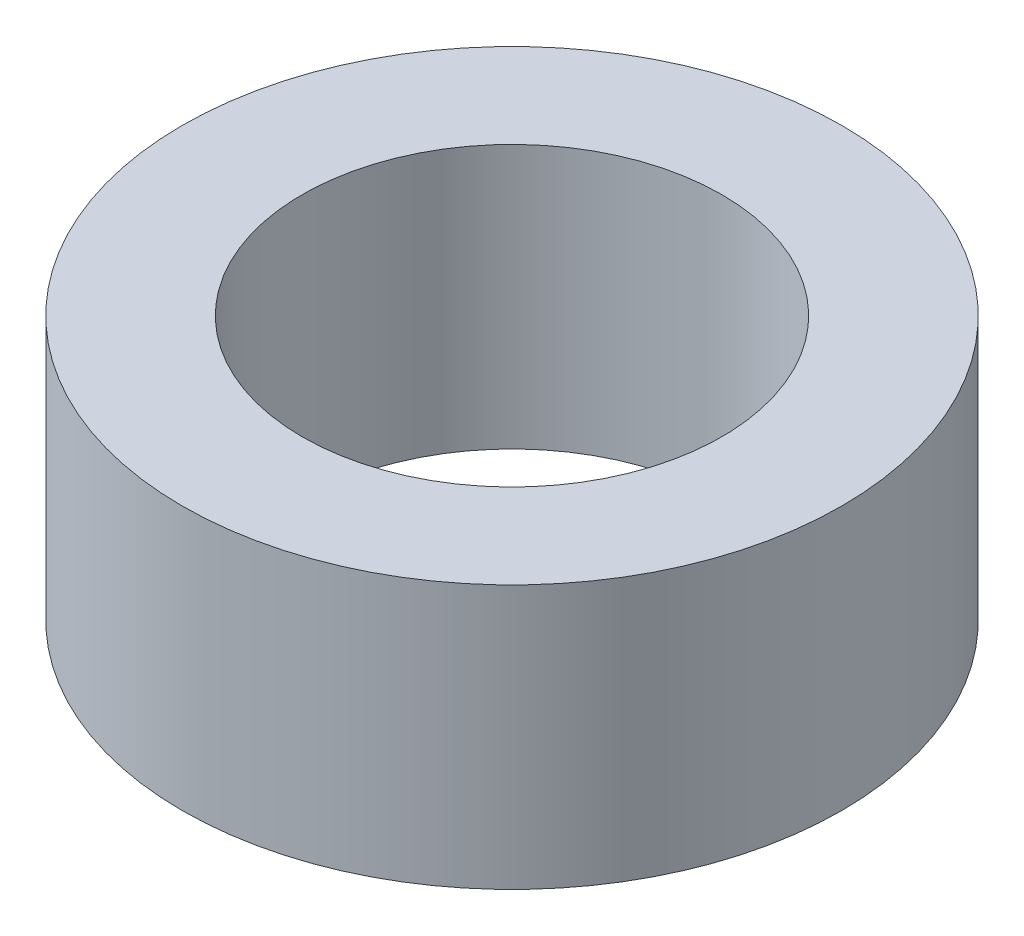
SolidWorks part; units mm, degrees
ref_plane "Front Plane" through (0, 0, 0) normal (0, 0, 1) x (1, 0, 0)
ref_plane "Top Plane" through (0, 0, 0) normal (0, 1, 0) x (1, 0, 0)
ref_plane "Right Plane" through (0, 0, 0) normal (1, 0, 0) x (0, 0, -1)
sketch "Sketch1" plane through (0, 0, 0) normal (0, 1, 0) x (1, 0, 0)
  circle A0 centre (0, 0) radius 27.5
  dimension "FLANGE_OD" = 55
extrude "Boss-Extrude1" add sketch "Sketch1" along normal blind 22
sketch "Sketch2" plane through (0, 0, 0) normal (0, 1, 0) x (1, 0, 0)
  circle A0 centre (0, 0) radius 17.5
  dimension "BORE_D" = 35
extrude "Cut-Extrude1" cut sketch "Sketch2" along normal through all
sketch "Sketch3" plane through (0, 22, 0) normal (0, 1, 0) x (1, 0, 0)
  circle A0 centre (0, 0) radius 11.6134 construction
  circle A1 centre (-11.6134, 0) radius 1.6547
  dimension "BOLT_D" = 3.3093
  dimension "BOLT_PCD" = 23.2267
extrude "Cut-Extrude2" cut sketch "Sketch3" against normal blind 14.8552 rebuild error yes
pattern_circular "CirPattern1" count 5 over 360 rebuild error yes
